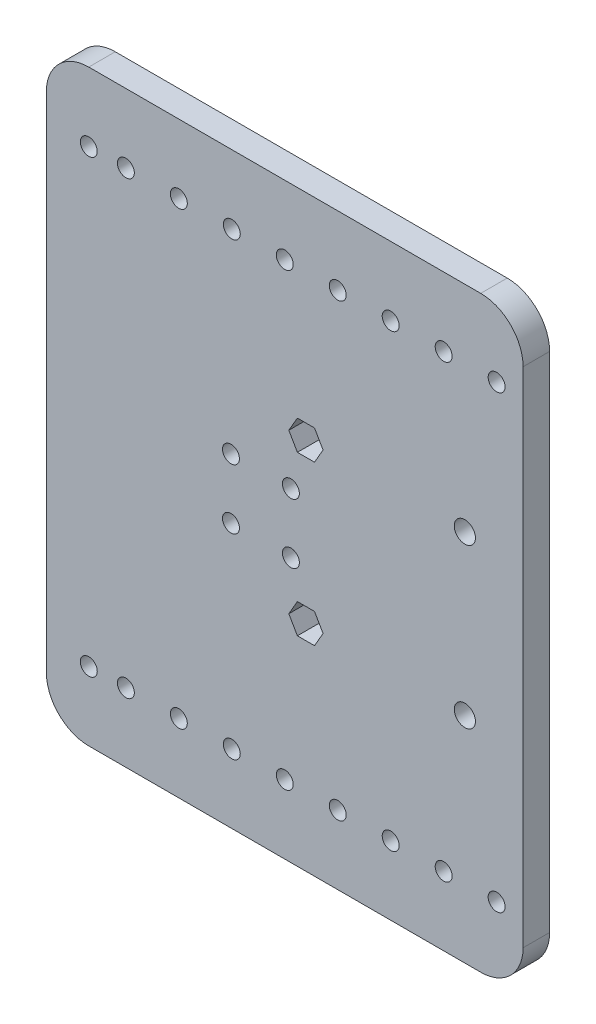
SolidWorks part; units mm, degrees
ref_plane "前视基准面" through (0, 0, 0) normal (0, 0, 1) x (1, 0, 0)
ref_plane "上视基准面" through (0, 0, 0) normal (0, 1, 0) x (1, 0, 0)
ref_plane "右视基准面" through (0, 0, 0) normal (1, 0, 0) x (0, 0, -1)
sketch "草图1" plane through (0, 0, 0) normal (0, 0, 1) x (1, 0, 0)
  line L1 (0, 0) -> (90, 0)
  line L2 (0, 0) -> (0, -111)
  line L3 (0, -111) -> (90, -111)
  line L4 (90, 0) -> (90, -111)
  line L5 (50.6166, -37.7) -> (47.3834, -37.7)
  line L6 (47.3834, -37.7) -> (45.7668, -40.5)
  line L7 (45.7668, -40.5) -> (47.3834, -43.3)
  line L8 (47.3834, -43.3) -> (50.6166, -43.3)
  line L9 (50.6166, -43.3) -> (52.2332, -40.5)
  line L10 (52.2332, -40.5) -> (50.6166, -37.7)
  line L11 (50.6166, -67.7) -> (47.3834, -67.7)
  line L12 (47.3834, -67.7) -> (45.7668, -70.5)
  line L13 (45.7668, -70.5) -> (47.3834, -73.3)
  line L14 (47.3834, -73.3) -> (50.6166, -73.3)
  line L15 (50.6166, -73.3) -> (52.2332, -70.5)
  line L16 (52.2332, -70.5) -> (50.6166, -67.7)
  circle A4 centre (79, -40.5) radius 2
  circle A5 centre (79, -70.5) radius 2
  circle A18 centre (85, -98) radius 1.6
  circle A19 centre (75, -98) radius 1.6
  circle A20 centre (65, -98) radius 1.6
  circle A21 centre (55, -98) radius 1.6
  circle A22 centre (45, -98) radius 1.6
  circle A23 centre (85, -13) radius 1.6
  circle A24 centre (75, -13) radius 1.6
  circle A25 centre (65, -13) radius 1.6
  circle A26 centre (55, -13) radius 1.6
  circle A27 centre (45, -13) radius 1.6
  circle A28 centre (35, -98) radius 1.6
  circle A29 centre (25, -98) radius 1.6
  circle A30 centre (15, -98) radius 1.6
  circle A31 centre (35, -13) radius 1.6
  circle A32 centre (25, -13) radius 1.6
  circle A33 centre (15, -13) radius 1.6
  circle A34 centre (8, -98) radius 1.6
  circle A35 centre (8, -13) radius 1.6
  circle A36 centre (49, -40.5) radius 2.8 construction
  circle A37 centre (49, -70.5) radius 2.8 construction
  point P27 (0, 0)
  point P33 (0, 0)
  dimension "D1" = 111
  dimension "D15" = 2
  dimension "D5" = 85
  dimension "D17" = 2
  dimension "D18" = 5.6
  dimension "D3" = 5.6
  dimension "D4" = 13
  dimension "D6" = 3.2
  dimension "D12" = 5
  dimension "D23" = 7
  dimension "D2" = 90
  dimension "D8" = 40.5
  dimension "D9" = 5
  dimension "D10" = 30
  dimension "D11" = 2
  dimension "D13" = 4
  dimension "D14" = 2
extrude "凸台-拉伸1" add sketch "草图1" along normal blind 5
fillet "圆角1" radius 8 4 edges at (0, -111, 2.5) (90, -111, 2.5) (90, 0, 2.5) (0, 0, 2.5)
sketch "内圈四孔_Ø3.2_PCD16" plane through (0, 0, 0) normal (0, 0, -1) x (-1, 0, 0)
  line L0 (-46.1569, -49.8431) -> (-34.8431, -61.1569) construction
  line L1 (-34.8431, -61.1569) -> (-34.8431, -49.8431) construction
  line L2 (-34.8431, -49.8431) -> (-46.1569, -49.8431) construction
  line L3 (-46.1569, -49.8431) -> (-46.1569, -61.1569) construction
  line L4 (-46.1569, -61.1569) -> (-34.8431, -61.1569) construction
  line L5 (-34.8431, -49.8431) -> (-46.1569, -61.1569) construction
  line L7 (-82, 0) -> (-8, 0) construction
  circle A15 centre (-46.1569, -49.8431) radius 1.6
  circle A16 centre (-34.8431, -49.8431) radius 1.6
  circle A17 centre (-34.8431, -61.1569) radius 1.6
  circle A18 centre (-46.1569, -61.1569) radius 1.6
  point P2 (-40.5, -55.5)
  dimension "D1" = 11.3137
  dimension "D3" = 55.5
  dimension "D2" = 16
extrude "内圈四孔_通孔_Ø3.2" cut sketch "内圈四孔_Ø3.2_PCD16" against normal blind 10
sketch "内圈沉孔_Ø6_PCD16" plane through (0, 0, 0) normal (0, 0, -1) x (-1, 0, 0)
  circle A10 centre (-46.1569, -54.3431) radius 3
  circle A11 centre (-34.8431, -54.3431) radius 3
  circle A12 centre (-34.8431, -65.6569) radius 3
  circle A13 centre (-46.1569, -65.6569) radius 3
extrude "内圈四孔_沉孔_Ø6深1" [suppressed] cut sketch "内圈沉孔_Ø6_PCD16" against normal blind 1
